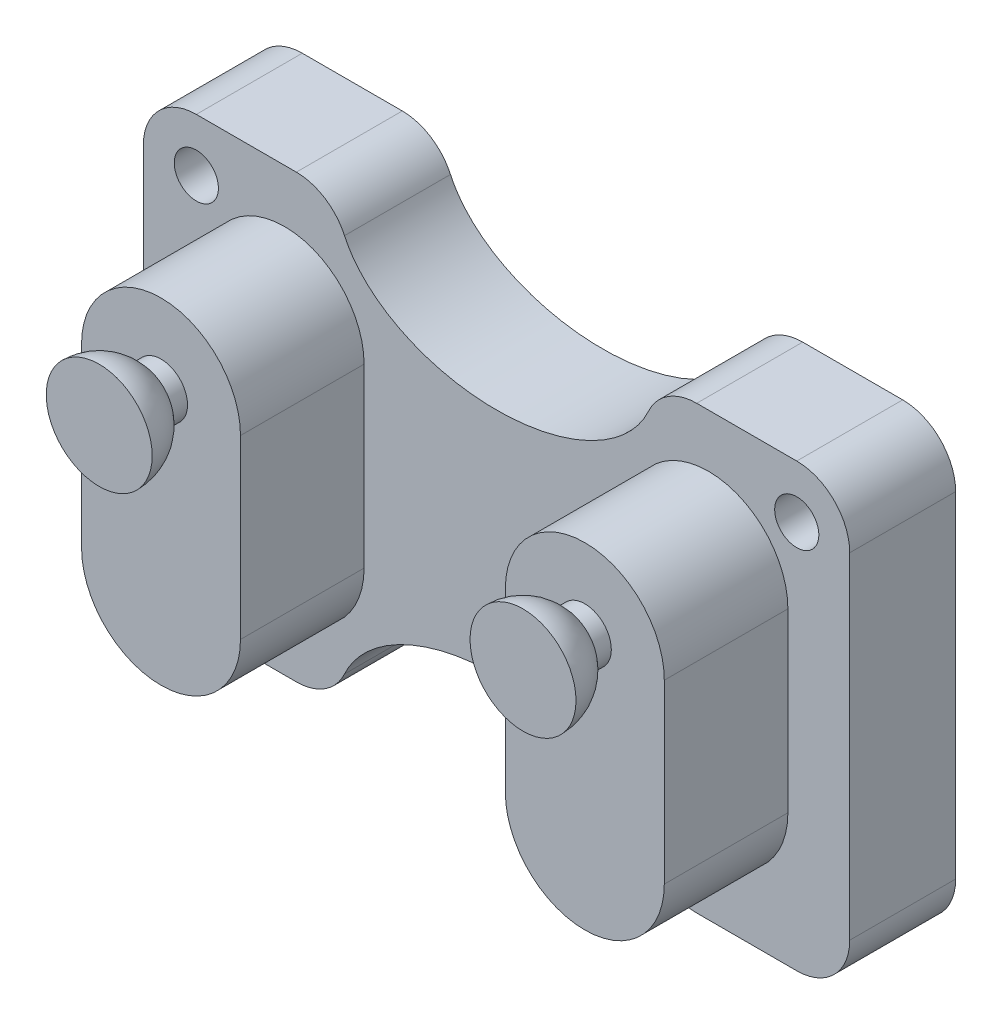
SolidWorks part; units mm, degrees
ref_plane "Ebene vorne" through (0, 0, 0) normal (0, 0, 1) x (1, 0, 0)
ref_plane "Ebene oben" through (0, 0, 0) normal (0, 1, 0) x (1, 0, 0)
ref_plane "Ebene rechts" through (0, 0, 0) normal (1, 0, 0) x (0, 0, -1)
sketch "Skizze1" plane through (0, 0, 0) normal (0, 0, 1) x (1, 0, 0)
  line L0 (621.0887, 0) -> (621.0887, 25) construction
  line L1 (0, 0) -> (40, 0)
  line L2 (0, 0) -> (0, 25)
  line L3 (0, 25) -> (40, 25)
  line L4 (40, 0) -> (40, 25)
  dimension "D1" = 40
  dimension "D2" = 25
extrude "Aufsatz-Linear austragen1" add sketch "Skizze1" along normal blind 6
ref_plane "Ebene2" through (0, 12.5, 0) normal (0, 1, 0) x (1, 0, 0)
ref_plane "Ebene1" through (20, 0, 0) normal (-1, 0, 0) x (0, 0, 1)
sketch "Skizze2" plane through (0, 0, 6) normal (0, 0, 1) x (1, 0, 0)
  line L0 (8, 17.5) -> (8, 7.5) construction
  line L1 (12.5, 17.5) -> (12.5, 7.5)
  line L2 (3.5, 17.5) -> (3.5, 7.5)
  line L3 (3.3, 12.5) -> (-3.3, 12.5) construction
  line L4 (20, 3.3) -> (20, -3.3) construction
  arc A0 (12.5, 17.5) -> (3.5, 17.5) centre (8, 17.5) ccw
  arc A1 (3.5, 7.5) -> (12.5, 7.5) centre (8, 7.5) ccw
  point P2 (8, 12.5)
  dimension "D1" = 4.5
  dimension "D2" = 10
  dimension "D3" = 0
  dimension "D4" = 12
extrude "Aufsatz-Linear austragen2" add sketch "Skizze2" along normal blind 7
mirror "Spiegeln1" about plane through (20, 0, 0) normal (-1, 0, 0) of "Aufsatz-Linear austragen2"
sketch "Skizze3" plane through (0, 0, 13) normal (0, 0, 1) x (1, 0, 0)
  line L1 (12.5, 7.5) -> (12.5, 17.5) construction
  circle A0 centre (8, 17.5) radius 1.5
  arc A1 (12.5, 17.5) -> (3.5, 17.5) centre (8, 17.5) ccw construction
  dimension "D2" = 3
  dimension "D1" = 0
  dimension "D3" = 4.5
extrude "Aufsatz-Linear austragen3" add sketch "Skizze3" along normal blind 3.5
mirror "Spiegeln2" about plane through (20, 0, 0) normal (-1, 0, 0) of "Aufsatz-Linear austragen3"
sketch "Skizze4" plane through (0, 0, 16.5) normal (0, 0, 1) x (1, 0, 0)
  line L0 (5, 17.5) -> (11, 17.5)
  arc A0 (5, 17.5) -> (11, 17.5) centre (8, 17.5) ccw
  dimension "D1" = 3
  dimension "D2" = 0
revolve "Rotation1" add sketch "Skizze4" angle 180 about L0
mirror "Spiegeln3" about plane through (20, 0, 0) normal (-1, 0, 0) of "Rotation1"
fillet "Verrundung1" radius 3 4 edges at (0, 0, 3) (40, 0, 3) (40, 25, 3) (0, 25, 3)
sketch "Skizze6" plane through (0, 0, 6) normal (0, 0, 1) x (1, 0, 0)
  line L0 (3, 0) -> (37, 0) construction
  ellipse E0 centre (20, 0) end of major axis (11, 0) minor radius 6
  dimension "D1" = 9
  dimension "D2" = 6
extrude "Schnitt-Linear austragen7" cut sketch "Skizze6" against normal up to surface (6 mm away) up to face at (20, 12.5, 0)
fillet "Verrundung2" radius 3 2 edges at (29, 0, 3) (11, 0, 3)
mirror "Spiegeln5" about plane through (0, 12.5, 0) normal (0, 1, 0) of "Schnitt-Linear austragen7"
fillet "Verrundung3" radius 3 2 edges at (29, 25, 3) (11, 25, 3)
sketch "Skizze7" plane through (0, 0, 6) normal (0, 0, 1) x (1, 0, 0)
  line L0 (0, 22) -> (0, 3) construction
  line L1 (8.6641, 25) -> (3, 25) construction
  circle A0 centre (3, 22) radius 1.25
  dimension "D1" = 2.5
  dimension "D2" = 3
  dimension "D3" = 3
extrude "Schnitt-Linear austragen8" cut sketch "Skizze7" against normal up to surface (6 mm away) up to face at (20, 12.5, 0)
mirror "Spiegeln6" about plane through (20, 0, 0) normal (-1, 0, 0) of "Schnitt-Linear austragen8"
